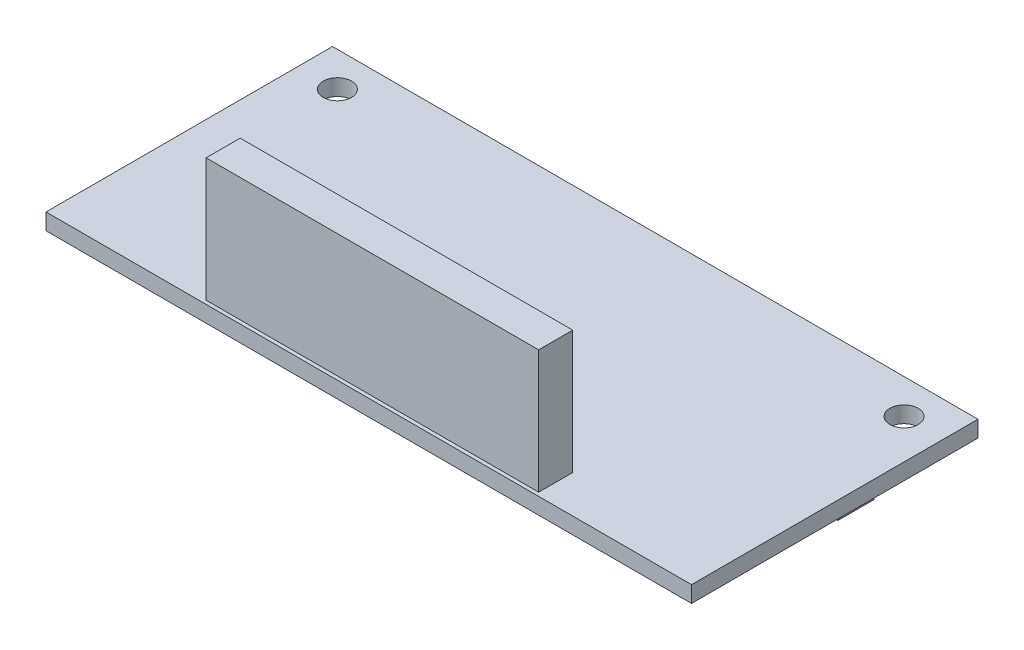
SolidWorks part; units mm, degrees
ref_plane "Front Plane" through (0, 0, 0) normal (0, 0, 1) x (1, 0, 0)
ref_plane "Top Plane" through (0, 0, 0) normal (0, 1, 0) x (1, 0, 0)
ref_plane "Right Plane" through (0, 0, 0) normal (1, 0, 0) x (0, 0, -1)
sketch "Sketch1" plane through (0, 0, 0) normal (0, 1, 0) x (1, 0, 0)
  line L0 (0, 10.033) -> (22.606, 10.033) construction
  line L1 (0, 0) -> (-22.606, 0)
  line L2 (0, 0) -> (0, 10.033)
  line L3 (0, 10.033) -> (-22.606, 10.033)
  line L4 (-22.606, 0) -> (-22.606, 10.033)
  line L5 (-22.606, 0) -> (-22.606, -10.033) construction
  circle A0 centre (-19.8438, 7.6136) radius 0.9906 construction
  point P9 (-19.8438, 8.6042)
  dimension "D3" = 1.9812
  dimension "D1" = 20.066
  dimension "D2" = 45.212
  dimension "D4" = 19.8438
  dimension "D5" = 1.4287
extrude "Boss-Extrude1" add sketch "Sketch1" along normal mid plane 1.143
mirror "Mirror1" about plane through (0, 0.5715, 0) normal (0, 0, -1) of "Boss-Extrude1"
sketch "Sketch2" plane through (0, 0.5715, 0) normal (0, 1, 0) x (1, 0, 0)
  circle A0 centre (-19.8438, 7.6136) radius 0.9906
extrude "Cut-Extrude1" cut sketch "Sketch2" against normal through all both and the other way through all
mirror "Mirror3" about plane through (0, 0, 0) normal (1, 0, 0) of bodies 103
sketch "Sketch3" plane through (0, 0.5715, 0) normal (0, 1, 0) x (1, 0, 0)
  line L1 (-11.6459, -9.779) -> (11.6459, -9.779)
  line L2 (-11.6459, -9.779) -> (-11.6459, -7.3914)
  line L3 (-11.6459, -7.3914) -> (11.6459, -7.3914)
  line L4 (11.6459, -9.779) -> (11.6459, -7.3914)
  line L5 (22.606, -10.033) -> (-22.606, -10.033) construction
  point P6 (0, -7.3914)
  dimension "D1" = 23.2918
  dimension "D2" = 2.3876
  dimension "D3" = 0.254
extrude "Boss-Extrude2" add sketch "Sketch3" along normal blind 8.636
sketch "Sketch4" plane through (0, -0.5715, 0) normal (0, -1, 0) x (1, 0, 0)
  line L1 (-21.5583, -3.8036) -> (-18.1292, -3.8036)
  line L2 (-21.5583, -3.8036) -> (-21.5583, -1.2636)
  line L3 (-21.5583, -1.2636) -> (-18.1292, -1.2636)
  line L4 (-18.1292, -3.8036) -> (-18.1292, -1.2636)
  line L5 (-21.5583, -3.8036) -> (-18.1292, -1.2636) construction
  line L6 (-21.5583, -1.2636) -> (-18.1292, -3.8036) construction
  point P0 (-19.8438, -2.5336)
  point P5 (-19.8438, -7.6136)
  dimension "D1" = 5.08
  dimension "D2" = 2.54
  dimension "D3" = 3.429
extrude "Boss-Extrude3" add sketch "Sketch4" along normal blind 1.143
pattern_linear "LPattern1" count 3 spacing 8.001 along (1, 0, 0) of "Boss-Extrude3"
mirror "Mirror4" about plane through (0, 0, 0) normal (1, 0, 0) of "LPattern1"
ref_axis "Axis1" through (-19.8438, -0.5715, -7.6136) along (0, 1, 0)
ref_axis "Axis2" through (19.8438, -0.5715, -7.6136) along (0, 1, 0)
ref_plane "Plane1" through (0, 0, -7.6136) normal (0, 0, 1) x (1, 0, 0)
